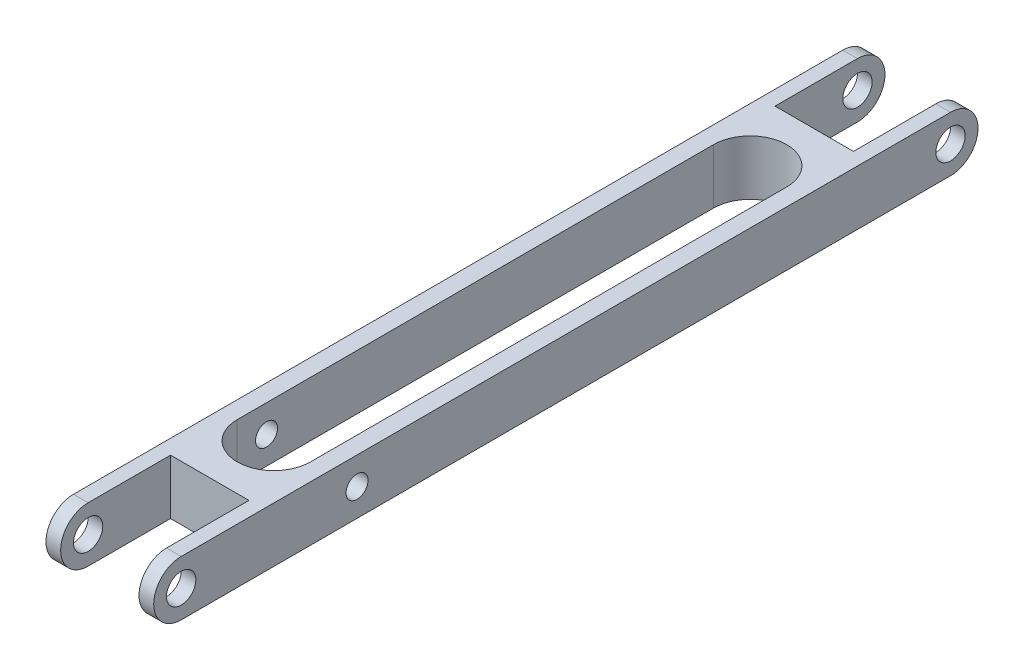
SolidWorks part; units mm, degrees
material "ABS"
ref_plane "前视基准面" through (0, 0, 0) normal (0, 0, 1) x (1, 0, 0)
ref_plane "上视基准面" through (0, 0, 0) normal (0, 1, 0) x (1, 0, 0)
ref_plane "右视基准面" through (0, 0, 0) normal (1, 0, 0) x (0, 0, -1)
sketch "草图2" plane through (0, 0, 0) normal (1, 0, 0) x (0, 0, -1)
  line L0 (-105, 7.5) -> (-105, -7.5) construction
  line L1 (-105, -7.5) -> (105, -7.5)
  line L3 (-105, 7.5) -> (105, 7.5)
  line L5 (-105, -7.5) -> (105, 7.5) construction
  line L6 (-105, 7.5) -> (105, -7.5) construction
  line L7 (105, 7.5) -> (105, -7.5) construction
  arc A0 (-105, 7.5) -> (-105, -7.5) centre (-105, 0) ccw
  arc A1 (105, 7.5) -> (105, -7.5) centre (105, 0) cw
  point P0 (0, 0)
  dimension "D1" = 15
  dimension "D2" = 210
extrude "凸台-拉伸1" add sketch "草图2" along normal blind 29.4
sketch "草图3" plane through (0, 7.5, 0) normal (0, 1, 0) x (1, 0, 0)
  line L1 (4, -112.5) -> (4, -82.5)
  line L2 (0, -112.5) -> (29.4, -112.5) construction
  line L3 (4, -82.5) -> (25.4, -82.5)
  line L4 (25.4, -82.5) -> (25.4, -112.5)
  line L5 (25.4, -112.5) -> (4, -112.5)
  line L6 (0, 105) -> (0, -105) construction
  line L7 (29.4, 105) -> (29.4, -105) construction
  line L10 (4, 112.5) -> (25.4, 112.5)
  line L14 (4, 112.5) -> (4, 82.5)
  line L15 (4, 82.5) -> (25.4, 82.5)
  line L16 (25.4, 82.5) -> (25.4, 112.5)
  line L17 (29.4, 105) -> (0, 105) construction
  dimension "D1" = 4
  dimension "D2" = 4
  dimension "D3" = 30
  dimension "D4" = 21.4
  dimension "D5" = 30
  dimension "D6" = 7.5
  dimension "D7" = 4
extrude "切除-拉伸1" cut sketch "草图3" against normal through all
sketch "草图4" plane through (29.4, 0, 0) normal (1, 0, 0) x (0, 0, -1)
  circle A0 centre (-105, 0) radius 4
  circle A1 centre (105, 0) radius 4
  dimension "D1" = 8
  dimension "D2" = 8
extrude "切除-拉伸2" cut sketch "草图4" against normal through all
sketch "草图5" plane through (0, -7.5, 0) normal (0, -1, 0) x (1, 0, 0)
  line L0 (14.7, 65) -> (14.7, -65) construction
  line L1 (24.7, 65) -> (24.7, -65)
  line L2 (4.7, 65) -> (4.7, -65)
  line L3 (0, 0) -> (14.7, 0) construction
  line L4 (0, 105) -> (0, -105) construction
  arc A0 (24.7, 65) -> (4.7, 65) centre (14.7, 65) ccw
  arc A1 (4.7, -65) -> (24.7, -65) centre (14.7, -65) ccw
  point P2 (14.7, 0)
  dimension "D1" = 20
  dimension "D2" = 14.7
  dimension "D3" = 130
extrude "切除-拉伸3" cut sketch "草图5" against normal through all
sketch "草图6" plane through (0, 0, 0) normal (-1, 0, 0) x (0, 0, 1)
  line L0 (57, 0) -> (0, 0) construction
  circle A1 centre (57, 0) radius 3
  circle A3 centre (105, 0) radius 4 construction
  dimension "D1" = 48
  dimension "D2" = 6
extrude "切除-拉伸4" cut sketch "草图6" against normal through all
